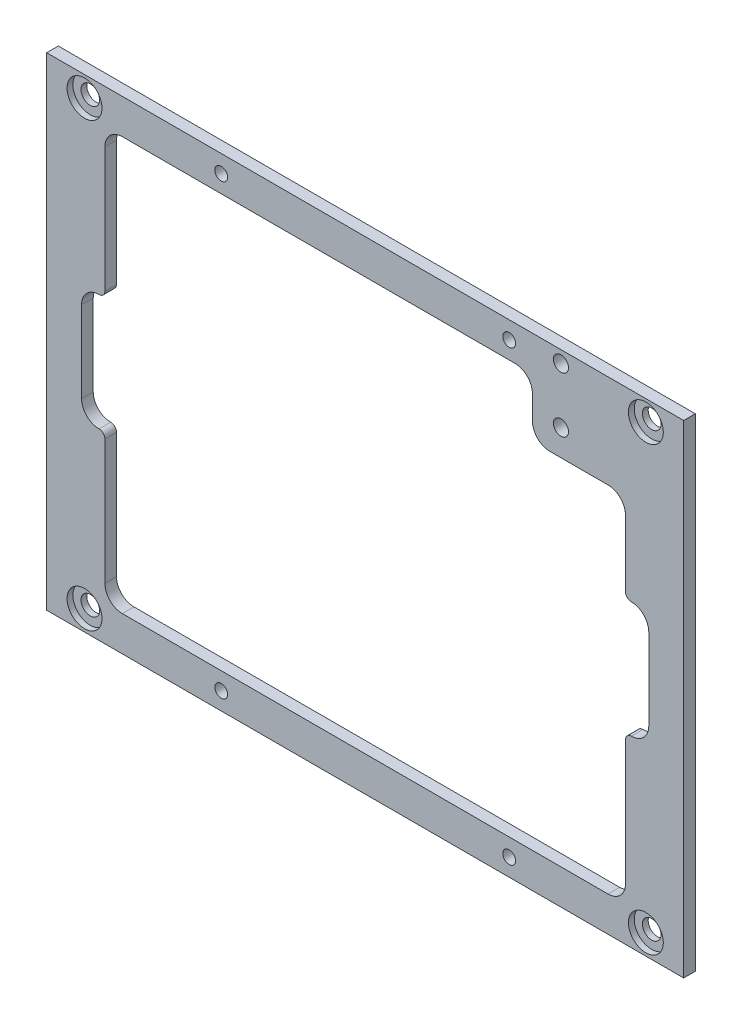
SolidWorks part; units mm, degrees
ref_plane "Front Plane" through (0, 0, 0) normal (0, 0, 1) x (1, 0, 0)
ref_plane "Top Plane" through (0, 0, 0) normal (0, 1, 0) x (1, 0, 0)
ref_plane "Right Plane" through (0, 0, 0) normal (1, 0, 0) x (0, 0, -1)
sketch "Sketch1" plane through (0, 0, 0) normal (0, 0, 1) x (1, 0, 0)
  line L0 (55.75, -83) -> (-55.75, -83) construction
  line L1 (-54.75, 0) -> (54.75, 0)
  line L2 (-54.75, 0) -> (-54.75, -83)
  line L3 (-54.75, -83) -> (54.75, -83)
  line L4 (54.75, 0) -> (54.75, -83)
  line L5 (-44.75, -31.5) -> (-48.75, -31.5)
  line L6 (28.75, -9) -> (28.75, -13.1)
  line L7 (-41.75, -6) -> (25.75, -6)
  line L8 (-44.75, -9) -> (-44.75, -31.5)
  line L9 (-41.75, -77) -> (41.75, -77)
  line L10 (44.75, -19.1) -> (44.75, -31.5)
  line L11 (31.75, -16.1) -> (41.75, -16.1)
  line L12 (54.75, -41.5) -> (48.75, -41.5) construction
  line L13 (48.75, -41.5) -> (48.75, -51.5)
  line L14 (44.75, -31.5) -> (48.75, -31.5)
  line L15 (-48.75, -31.5) -> (-48.75, -51.5)
  line L16 (44.75, -51.5) -> (48.75, -51.5)
  line L17 (48.75, -31.5) -> (48.75, -41.5)
  line L18 (44.75, -51.5) -> (44.75, -74)
  line L19 (-48.75, -51.5) -> (-44.75, -51.5)
  line L20 (-44.75, -51.5) -> (-44.75, -74)
  arc A0 (41.75, -77) -> (44.75, -74) centre (41.75, -74) ccw
  arc A1 (-44.75, -74) -> (-41.75, -77) centre (-41.75, -74) ccw
  arc A2 (-41.75, -6) -> (-44.75, -9) centre (-41.75, -9) ccw
  arc A3 (28.75, -9) -> (25.75, -6) centre (25.75, -9) ccw
  arc A4 (41.75, -16.1) -> (44.75, -19.1) centre (41.75, -19.1) cw
  arc A5 (28.75, -13.1) -> (31.75, -16.1) centre (31.75, -13.1) ccw
  point P24 (28.75, -6)
  point P29 (28.75, -16.1)
  dimension "D6" = 3
  dimension "D8" = 3
  dimension "D2" = 10
  dimension "D3" = 10
  dimension "D4" = 6
  dimension "D5" = 6
  dimension "D7" = 73.5
  dimension "D9" = 16.1
  dimension "D10" = 4
  dimension "D11" = 10
  dimension "D12" = 10
  dimension "D13" = 89.5
  dimension "D14" = 83
  dimension "D15" = 4
  dimension "D16" = 20
  dimension "D17" = 31.5
extrude "Boss-Extrude1" add sketch "Sketch1" along normal blind 2
hole_wizard "Ø3.2 (3.2) Diameter Hole2" positions "Sketch4" profile "Sketch3" hole size "Ø3.2" standard "Ansi Metric" end condition up to next
sketch "Sketch4" plane through (0, 0, 2) normal (0, 0, 1) x (1, 0, 0)
  line L0 (-54.75, 0) -> (-54.75, -83) construction
  line L1 (54.75, 0) -> (-54.75, 0) construction
  line L2 (-54.75, -83) -> (54.75, -83) construction
  line L3 (54.75, -83) -> (54.75, 0) construction
  point P0 (-48.25, -3.5)
  point P1 (-48.25, -79.5)
  point P3 (48.25, -79.5)
  point P5 (48.25, -3.5)
  dimension "D1" = 6.5
  dimension "D2" = 3.5
  dimension "D3" = 6.5
  dimension "D4" = 3.5
  dimension "D5" = 3.5
  dimension "D6" = 6.5
  dimension "D7" = 6.5
  dimension "D8" = 3.5
sketch "Sketch3" plane through (-48.25, -3.5, 2) normal (1, 0, 0) x (0, -1, 0)
  line L0 (0, 0) -> (0, 2)
  line L1 (0, 2) -> (1.6, 2)
  line L2 (1.6, 2) -> (1.6, 0)
  line L5 (1.6, 0) -> (0, 0)
  line L11 (0, -6.35) -> (0, 107.95) construction
  dimension "Thru Hole Dia." = 3.2
  dimension "Thru Hole Depth" = 2
hole_wizard "Ø2.6 (2.6) Diameter Hole2" positions "Sketch6" profile "Sketch5" hole size "Ø2.6" standard "Ansi Metric" end condition up to next
sketch "Sketch6" plane through (0, 0, 2) normal (0, 0, 1) x (1, 0, 0)
  line L1 (41.75, -16.1) -> (31.75, -16.1) construction
  line L2 (54.75, -83) -> (54.75, 0) construction
  point P0 (33.65, -11.6)
  dimension "D1" = 21.1
  dimension "D2" = 4.5
sketch "Sketch5" plane through (33.65, -11.6, 2) normal (1, 0, 0) x (0, -1, 0)
  line L0 (0, 0) -> (0, 2)
  line L1 (0, 2) -> (1.3, 2)
  line L2 (1.3, 2) -> (1.3, 0)
  line L5 (1.3, 0) -> (0, 0)
  line L11 (0, -6.35) -> (0, 107.95) construction
  dimension "Thru Hole Dia." = 2.6
  dimension "Thru Hole Depth" = 2
hole_wizard "Ø2.6 (2.6) Diameter Hole1" positions "Sketch8" profile "Sketch7" hole size "Ø2.6" standard "Ansi Metric" end condition up to next
sketch "Sketch8" plane through (0, 0, 2) normal (0, 0, 1) x (1, 0, 0)
  line L1 (54.75, -83) -> (54.75, 0) construction
  circle A1 centre (33.65, -11.6) radius 1.3 construction
  point P0 (33.65, -2.07)
  dimension "D2" = 9.53
  dimension "D1" = 21.1
sketch "Sketch7" plane through (33.65, -2.07, 2) normal (1, 0, 0) x (0, -1, 0)
  line L0 (0, 0) -> (0, 2)
  line L1 (0, 2) -> (1.3, 2)
  line L2 (1.3, 2) -> (1.3, 0)
  line L5 (1.3, 0) -> (0, 0)
  line L11 (0, -6.35) -> (0, 107.95) construction
  dimension "Thru Hole Dia." = 2.6
  dimension "Thru Hole Depth" = 2
sketch "Sketch9" plane through (0, 0, 2) normal (0, 0, 1) x (1, 0, 0)
  circle A0 centre (-48.25, -3.5) radius 3
  circle A1 centre (48.25, -3.5) radius 3
  circle A2 centre (48.25, -79.5) radius 3
  circle A3 centre (-48.25, -79.5) radius 3
  dimension "D1" = 6
  dimension "D2" = 6
  dimension "D3" = 6
  dimension "D4" = 6
extrude "Cut-Extrude1" cut sketch "Sketch9" against normal blind 1
hole_wizard "Ø2.2 (2.2) Diameter Hole1" positions "Sketch11" profile "Sketch10" hole size "Ø2.2" standard "Ansi Metric" end condition up to next
sketch "Sketch11" plane through (0, 0, 2) normal (0, 0, 1) x (1, 0, 0)
  line L0 (-54.75, 0) -> (-54.75, -83) construction
  line L1 (54.75, 0) -> (-54.75, 0) construction
  line L2 (54.75, -83) -> (54.75, 0) construction
  line L3 (-54.75, -83) -> (54.75, -83) construction
  point P0 (-24.75, -3)
  point P1 (24.75, -3)
  point P3 (-24.75, -80)
  point P5 (24.75, -80)
  dimension "D1" = 30
  dimension "D2" = 3
  dimension "D3" = 30
  dimension "D4" = 3
  dimension "D5" = 3
  dimension "D6" = 30
  dimension "D7" = 30
  dimension "D8" = 3
sketch "Sketch10" plane through (-24.75, -3, 2) normal (1, 0, 0) x (0, -1, 0)
  line L0 (0, 0) -> (0, 2)
  line L1 (0, 2) -> (1.1, 2)
  line L2 (1.1, 2) -> (1.1, 0)
  line L5 (1.1, 0) -> (0, 0)
  line L11 (0, -6.35) -> (0, 107.95) construction
  dimension "Thru Hole Dia." = 2.2
  dimension "Thru Hole Depth" = 2
fillet "Fillet1" radius 1 4 edges at (44.75, -51.5, 1) (44.75, -31.5, 1) (-44.75, -31.5, 1) (-44.75, -51.5, 1)
fillet "Fillet2" radius 3 4 edges at (48.75, -31.5, 1) (48.75, -51.5, 1) (-48.75, -51.5, 1) (-48.75, -31.5, 1)
